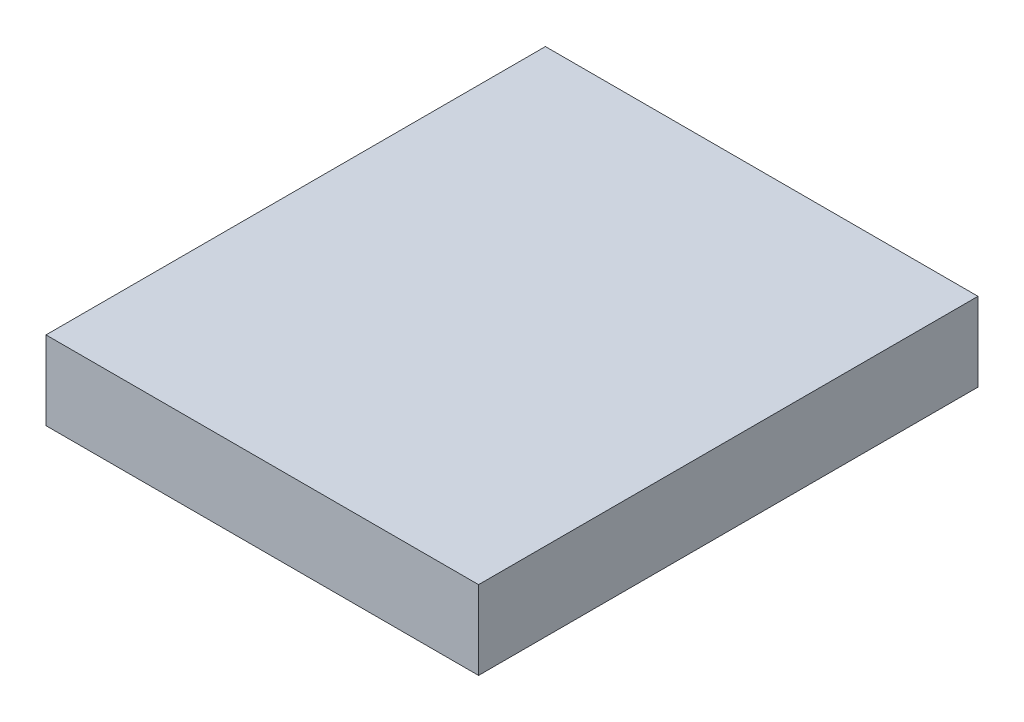
SolidWorks part; units mm, degrees
ref_plane "Front Plane" through (0, 0, 0) normal (0, 0, 1) x (1, 0, 0)
ref_plane "Top Plane" through (0, 0, 0) normal (0, 1, 0) x (1, 0, 0)
ref_plane "Right Plane" through (0, 0, 0) normal (1, 0, 0) x (0, 0, -1)
sketch "Sketch1" plane through (0, 0, 0) normal (0, 0, 1) x (1, 0, 0)
  line L0 (0, 0) -> (12.0089, 12.0089) construction
  line L1 (0, 0) -> (11, 0) construction
  line L2 (0, 0) -> (5.6569, 5.6569) construction
  line L3 (6.0199, 3.5362) -> (6.125, 3.5362)
  line L4 (-6.0199, 3.5362) -> (-6.125, 3.5362)
  line L5 (-7.875, 5.2862) -> (-7.875, 21.5362)
  line L6 (7.875, 5.2862) -> (7.875, 21.5362)
  line L7 (-1.9515, 5.1262) -> (-2.3732, 4.7371)
  line L8 (2.3732, 4.7371) -> (1.9515, 5.1262)
  line L9 (-7.875, 21.5362) -> (-33, 21.5362)
  line L10 (-33, 21.5362) -> (-33, 33.5362)
  line L11 (-33, 33.5362) -> (33, 33.5362)
  line L12 (33, 33.5362) -> (33, 21.5362)
  line L13 (33, 21.5362) -> (7.875, 21.5362)
  line L14 (7.875, 21.5362) -> (-7.875, 21.5362)
  circle A0 centre (0, 0) radius 11
  circle A4 centre (5.6569, 5.6569) radius 1.75
  circle A5 centre (5.6569, -5.6569) radius 1.75
  circle A6 centre (-5.6569, -5.6569) radius 1.75
  circle A7 centre (-5.6569, 5.6569) radius 1.75
  circle A8 centre (0, 0) radius 5.1
  arc A9 (6.0199, 3.5362) -> (1.9515, 5.1262) centre (6.0199, 9.5362) cw
  arc A10 (-1.9515, 5.1262) -> (-6.0199, 3.5362) centre (-6.0199, 9.5362) cw
  arc A11 (-6.125, 3.5362) -> (-7.875, 5.2862) centre (-6.125, 5.2862) cw
  arc A12 (6.125, 3.5362) -> (7.875, 5.2862) centre (6.125, 5.2862) ccw
  arc A13 (2.3732, 4.7371) -> (-2.3732, 4.7371) centre (0, 2.1646) ccw
  point P27 (3.675, 3.5362)
  point P30 (-3.675, 3.5362)
  point P33 (-7.875, 3.5362)
  point P38 (0, 6.9265)
  dimension "D1" = 22
  dimension "D4" = 3.5
  dimension "D5" = 10.2
  dimension "D10" = 6
  dimension "D11" = 1.75
  dimension "D12" = 1.75
  dimension "D13" = 3.5
  dimension "D2" = 45
  dimension "D3" = 8
  dimension "D6" = 5
  dimension "D7" = 18
  dimension "D8" = 4.2
  dimension "D9" = 15.75
  dimension "D14" = 12
  dimension "D15" = 25.125
  dimension "D16" = 66
extrude "Boss-Extrude1" add sketch "Sketch1" along normal mid plane 76.2 contours A0 L6 L13 L12 L11 L10 L9 L5 region at (0, 27.5362, 0)
extrude "Boss-Extrude3" add sketch "Sketch1<4>" along normal mid plane 15 contours A0 L6 L14 L5 | A13 L8 A9 L3 A12 L6 A0 L5 A11 L4 A10 L7 A7 A4 region at (0, 7.6228, 0) region at (0, 15.7132, 0)
sketch "Sketch1<4>" plane through (0, 0, 0) normal (0, 0, 1) x (1, 0, 0) same geometry as "Sketch1"
extrude "Cut-Extrude1" cut sketch "Sketch1<5>" against normal mid plane 3.5 contours A13 L8 A9 L3 A12 L6 A0 L5 A11 L4 A10 L7 A7 A4 region at (0, 7.6228, 0)
sketch "Sketch1<5>" plane through (0, 0, 0) normal (0, 0, 1) x (1, 0, 0) same geometry as "Sketch1"
